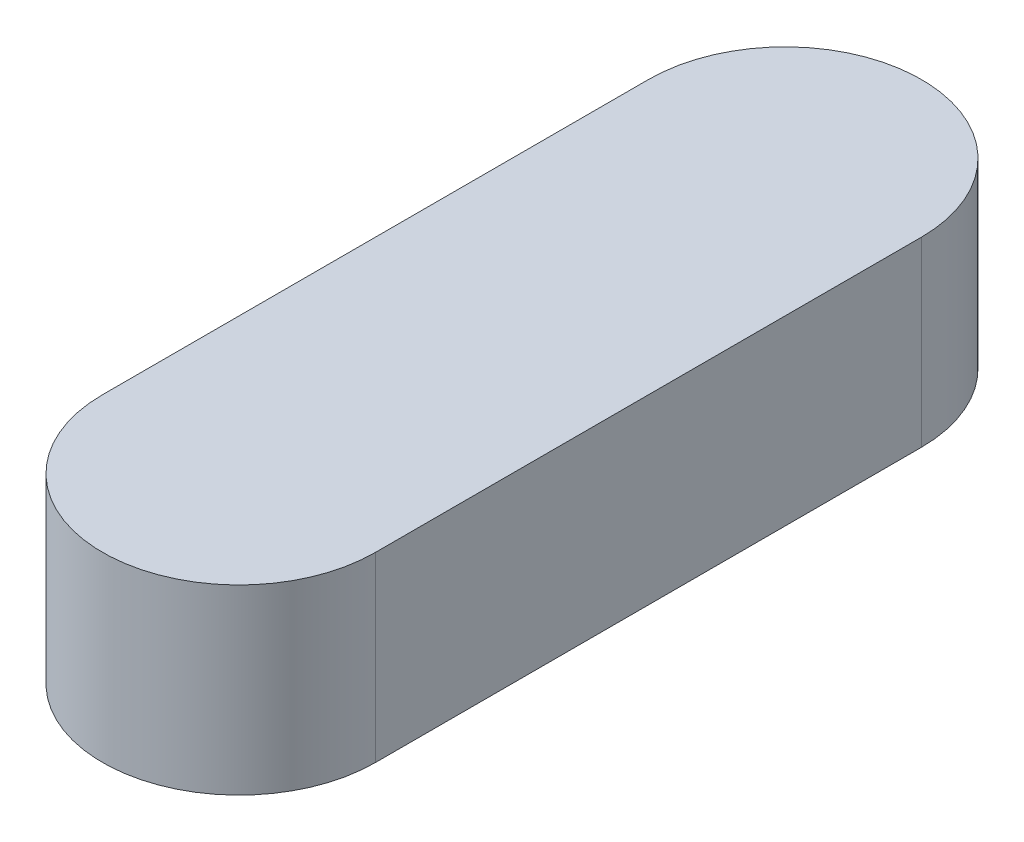
SolidWorks part; units mm, degrees
ref_plane "Přední rovina" through (0, 0, 0) normal (0, 0, 1) x (1, 0, 0)
ref_plane "Vrchní rovina" through (0, 0, 0) normal (0, 1, 0) x (1, 0, 0)
ref_plane "Pravá rovina" through (0, 0, 0) normal (1, 0, 0) x (0, 0, -1)
sketch "Skica1" plane through (0, 0, 0) normal (0, 1, 0) x (1, 0, 0)
  line L0 (-6, 12) -> (-6, -12)
  line L1 (6, -12) -> (6, 12)
  line L2 (0, 12) -> (0, -12) construction
  arc A0 (-6, -12) -> (6, -12) centre (0, -12) ccw
  arc A1 (6, 12) -> (-6, 12) centre (0, 12) ccw
  dimension "l" = 36
  dimension "b" = 12
extrude "Vysunout1" add sketch "Skica1" along normal mid plane 8
chamfer "Zkosit1" [suppressed] distance 0.7 angle 45
